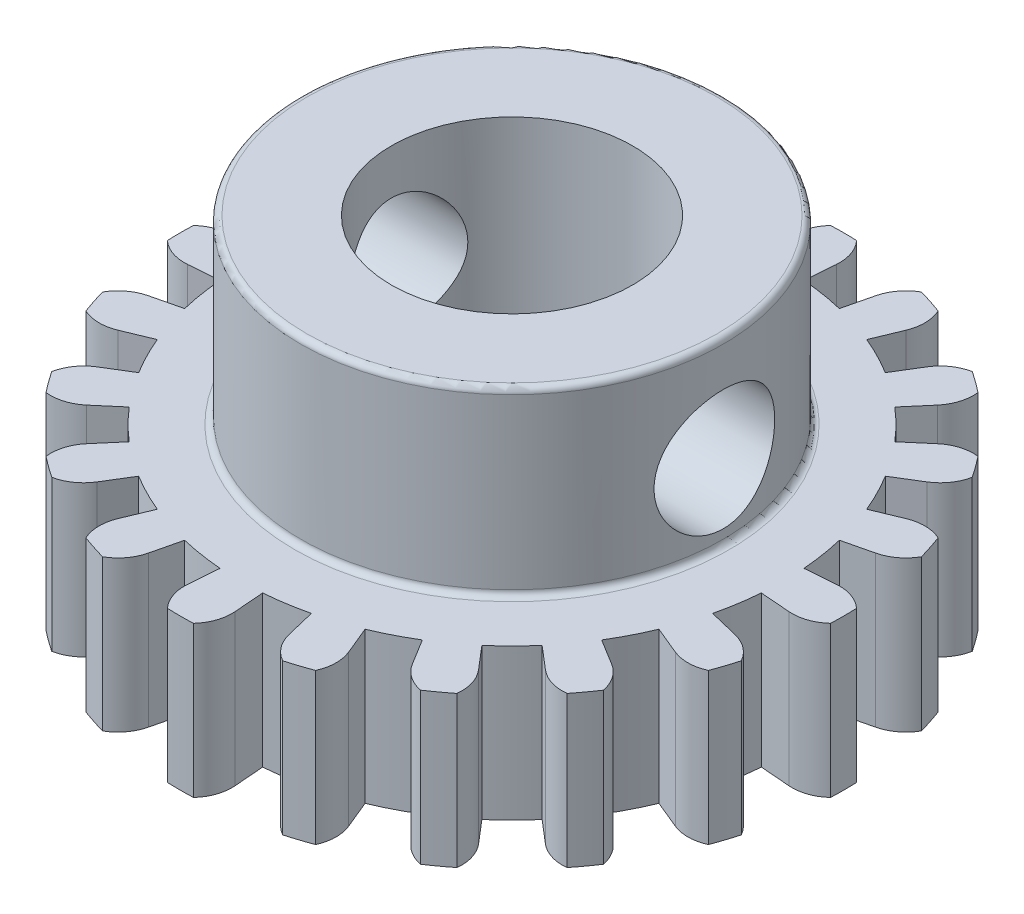
SolidWorks part; units mm, degrees
material "0.7060 (EN-GJS-600-3)"
ref_plane "Front" through (0, 0, 0) normal (0, 0, 1) x (1, 0, 0)
ref_plane "Top" through (0, 0, 0) normal (0, 1, 0) x (1, 0, 0)
ref_plane "Right" through (0, 0, 0) normal (1, 0, 0) x (0, 0, -1)
sketch "Sketch1" plane through (0, 0, 0) normal (0, 1, 0) x (1, 0, 0)
  line L0 (0, 0) -> (14.1605, 0) construction
  line L1 (0, 0) -> (8.8892, 1.4079) construction
  line L2 (0, 0) -> (13.7829, 1.0847) construction
  line L3 (0, 0) -> (10.7023, 0.4205) construction
  line L4 (8.9723, 0.7061) -> (9.9692, 0.7846)
  line L5 (0, 0) -> (8.8892, 1.4079)
  line L6 (8.9723, -0.7061) -> (9.9692, -0.7846)
  line L7 (0, 0) -> (8.8892, -1.4079)
  circle A0 centre (0, 0) radius 11 construction
  circle A1 centre (0, 0) radius 10 construction
  circle A2 centre (0, 0) radius 9 construction
  arc A3 (9.9692, 0.7846) -> (10.9915, 0.4319) centre (10.0754, -0.5654) cw
  arc A4 (8.9723, 0.7061) -> (8.8892, 1.4079) centre (0, 0) ccw
  arc A5 (10.9915, 0.4319) -> (10.9915, -0.4319) centre (0, 0) cw
  arc A6 (9.9692, -0.7846) -> (10.9915, -0.4319) centre (10.0754, 0.5654) ccw
  arc A7 (8.9723, -0.7061) -> (8.8892, -1.4079) centre (0, 0) cw
  dimension "D1" = 22
  dimension "D2" = 20
  dimension "D3" = 2
  dimension "D4" = 9
  dimension "D5" = 4.5
  dimension "D6" = 2.25
extrude "Boss-Extrude1" add sketch "Sketch1" along normal blind 5
pattern_circular "CirPattern1" count 20 over 360 about axis through (0, 5, 0) along (0, -1, 0) of "Boss-Extrude1" reverse direction yes
sketch "Sketch2" plane through (0, 5, 0) normal (0, 1, 0) x (1, 0, 0)
  circle A0 centre (0, 0) radius 7
  circle A1 centre (0, 0) radius 4
  dimension "D1" = 14
  dimension "D2" = 8
extrude "Cut-Extrude1" cut sketch "Sketch2" against normal through all both and the other way through all contours A1
extrude "Boss-Extrude2" add sketch "Sketch2<3>" along normal blind 6
sketch "Sketch2<3>" plane through (0, 5, 0) normal (0, 1, 0) x (1, 0, 0) same geometry as "Sketch2"
fillet "Fillet1" radius 0.2 2 edges at (0, 5, -7) (0, 11, 7)
sketch "Sketch3" plane through (0, 0, 0) normal (1, 0, 0) x (0, 0, -1)
  circle A0 centre (0, 7.5) radius 2
  dimension "D1" = 4
  dimension "D2" = 7.5
extrude "Cut-Extrude2" cut sketch "Sketch3" against normal through all both and the other way through all
